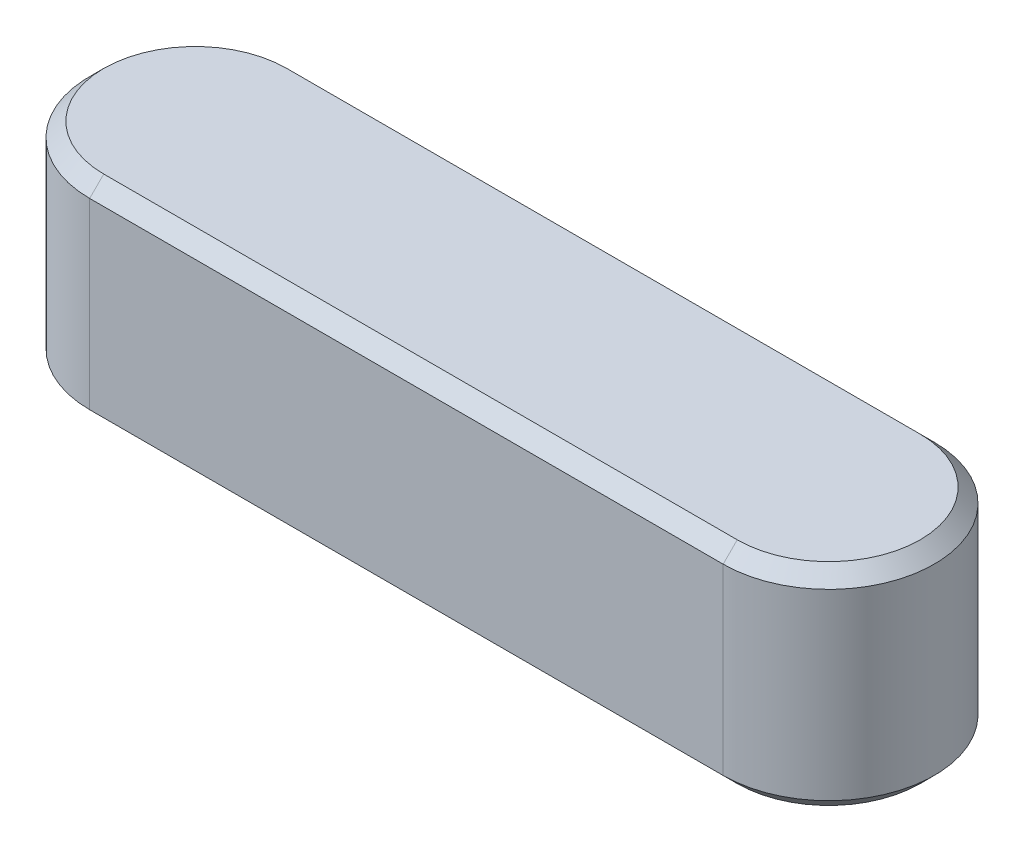
SolidWorks part; units mm, degrees
material "S45C"
ref_plane "Front Plane" through (0, 0, 0) normal (0, 0, 1) x (1, 0, 0)
ref_plane "Top Plane" through (0, 0, 0) normal (0, 1, 0) x (1, 0, 0)
ref_plane "Right Plane" through (0, 0, 0) normal (1, 0, 0) x (0, 0, -1)
sketch "Sketch1" plane through (0, 0, 0) normal (0, 1, 0) x (1, 0, 0)
  line L0 (-6, 0) -> (6, 0) construction
  line L1 (0, 1.5) -> (0, -1.5) construction
  line L3 (-6, 1.5) -> (6, 1.5)
  line L4 (-6, 1.5) -> (-6, -1.5)
  line L5 (-6, -1.5) -> (6, -1.5)
  line L6 (6, 1.5) -> (6, -1.5)
  dimension "L" = 12
  dimension "B" = 3
extrude "Boss-Extrude1" add sketch "Sketch1" along normal blind 3
chamfer "Chamfer1" [suppressed] distance 0.2 angle 45
fillet "Fillet1" 2 edges at (-6, 1.5, 1.5) (-6, 1.5, -1.5) type full round first side face at (0, 1.5, 1.5) second side face at (0, 1.5, -1.5) middle face at (-6, 1.5, 0)
fillet "Fillet2" 2 edges at (6, 1.5, 1.5) (6, 1.5, -1.5) type full round first side face at (0.75, 1.5, 1.5) second side face at (0.75, 1.5, -1.5) middle face at (6, 1.5, 0)
chamfer "Chamfer2" distance 0.2 angle 45 8 edges at (0, 0, -1.5) (-6, 0, 0) (6, 0, 0) (0, 0, 1.5) (0, 3, -1.5) (-6, 3, 0) (6, 3, 0) (0, 3, 1.5)
